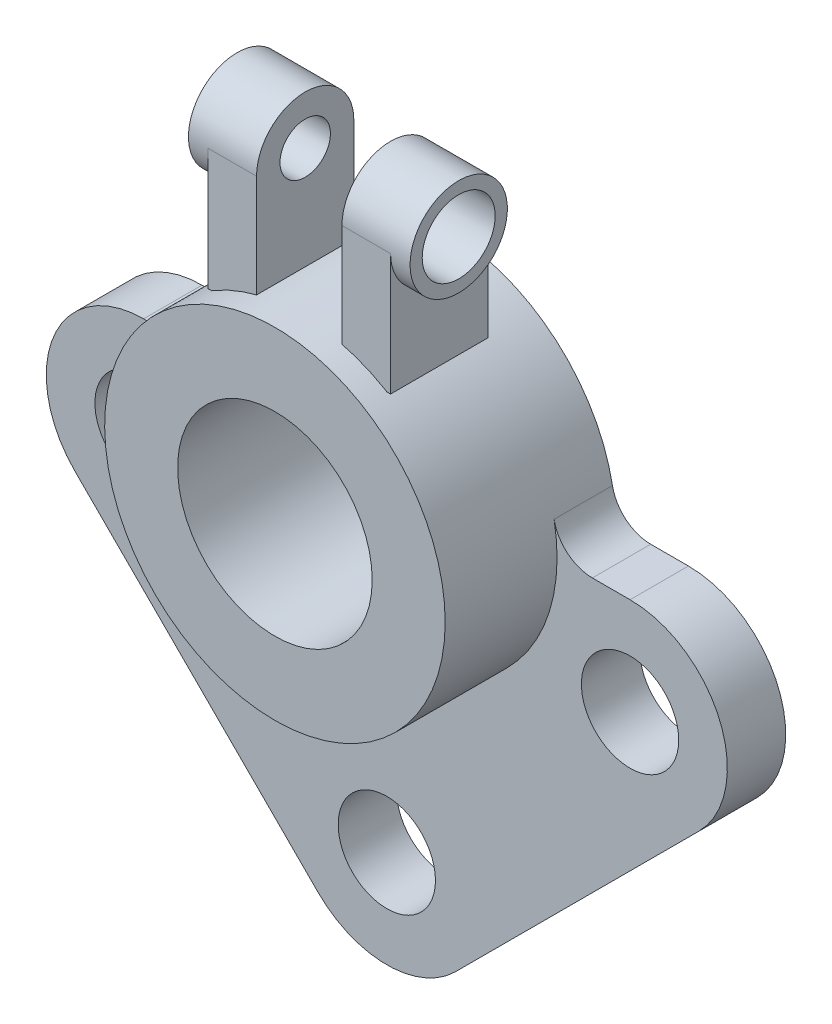
SolidWorks part; units mm, degrees
ref_plane "Plan de face" through (0, 0, 0) normal (0, 0, 1) x (1, 0, 0)
ref_plane "Plan de dessus" through (0, 0, 0) normal (0, 1, 0) x (1, 0, 0)
ref_plane "Plan de droite" through (0, 0, 0) normal (1, 0, 0) x (0, 0, -1)
sketch "Esquisse1" plane through (0, 0, 0) normal (0, 0, 1) x (1, 0, 0)
  circle A0 centre (0, 0) radius 35
  circle A1 centre (0, 0) radius 20
  dimension "D1" = 70
  dimension "D2" = 40
extrude "Boss.-Extru.1" add sketch "Esquisse1" along normal blind 35
sketch "Esquisse2" plane through (0, 0, 0) normal (0, 0, 1) x (1, 0, 0)
  line L0 (14.1421, -84.1421) -> (64.1421, -34.1421)
  line L4 (-64.1421, -34.1421) -> (-14.1421, -84.1421)
  line L5 (0, -98.2843) -> (0, -11.7723) construction
  line L6 (50, 0) -> (35, 0)
  line L7 (-50, 0) -> (-35, 0)
  arc A0 (14.1421, -84.1421) -> (-14.1421, -84.1421) centre (0, -70) cw
  circle A1 centre (0, 0) radius 35 construction
  arc A2 (64.1421, -34.1421) -> (50, 0) centre (50, -20) ccw
  arc A3 (-50, 0) -> (-64.1421, -34.1421) centre (-50, -20) ccw
  arc A4 (-35, 0) -> (35, 0) centre (0, 0) ccw
  circle A5 centre (50, -20) radius 10
  circle A6 centre (0, -70) radius 10
  circle A7 centre (-50, -20) radius 10
  dimension "D1" = 20
  dimension "D2" = 20
  dimension "D3" = 100
  dimension "D5" = 20
  dimension "D4" = 50
extrude "Boss.-Extru.2" add sketch "Esquisse2" along normal blind 12
fillet "Congé1" radius 8 2 edges at (-35, 0, 6) (35, 0, 6)
ref_plane "Plan1" through (0, 30, 0) normal (0, 1, 0) x (1, 0, 0)
sketch "Esquisse4" plane through (0, 30, 0) normal (0, 1, 0) x (1, 0, 0)
  line L0 (0, 31.446) -> (0, -63.7078) construction
  line L1 (-35, -35) -> (35, -35) construction
  line L2 (8.7766, -30) -> (18.7766, -30)
  line L3 (8.7766, -30) -> (8.7766, -10)
  line L4 (8.7766, -10) -> (18.7766, -10)
  line L5 (18.7766, -30) -> (18.7766, -10)
  line L6 (-8.7766, -10) -> (-18.7766, -10)
  line L7 (-8.7766, -30) -> (-8.7766, -10)
  line L8 (-8.7766, -30) -> (-18.7766, -30)
  line L9 (-18.7766, -30) -> (-18.7766, -10)
  dimension "D1" = 5
  dimension "D2" = 20
  dimension "D3" = 10
extrude "Boss.-Extru.3" add sketch "Esquisse4" along normal blind 25 separate body
sketch "Esquisse6" plane through (-8.7766, 0, 0) normal (1, 0, 0) x (0, 0, -1)
  line L0 (-30, 55) -> (-10, 55) construction
  circle A0 centre (-20, 55) radius 10
extrude "Boss.-Extru.4" add sketch "Esquisse6" against normal blind 14
sketch "Esquisse8" plane through (-8.7766, 0, 0) normal (1, 0, 0) x (0, 0, -1)
  circle A0 centre (-20, 55) radius 5.1823
extrude "Enlèv. mat.-Extru.1" cut sketch "Esquisse8" against normal through all
sketch "Esquisse12" plane through (0, 30, 0) normal (0, 1, 0) x (1, 0, 0)
  line L0 (0, 28.6076) -> (0, -56.099) construction
sketch "Esquisse14" plane through (8.7766, 0, 0) normal (-1, 0, 0) x (0, 0, 1)
  line L0 (10, 55) -> (30, 55) construction
  circle A0 centre (20, 55) radius 10
extrude "Boss.-Extru.5" add sketch "Esquisse14" against normal blind 14
sketch "Esquisse15" plane through (8.7766, 0, 0) normal (-1, 0, 0) x (0, 0, 1)
  circle A0 centre (20, 55) radius 7.5
  dimension "D1" = 15
extrude "Enlèv. mat.-Extru.2" cut sketch "Esquisse15" against normal blind 14
